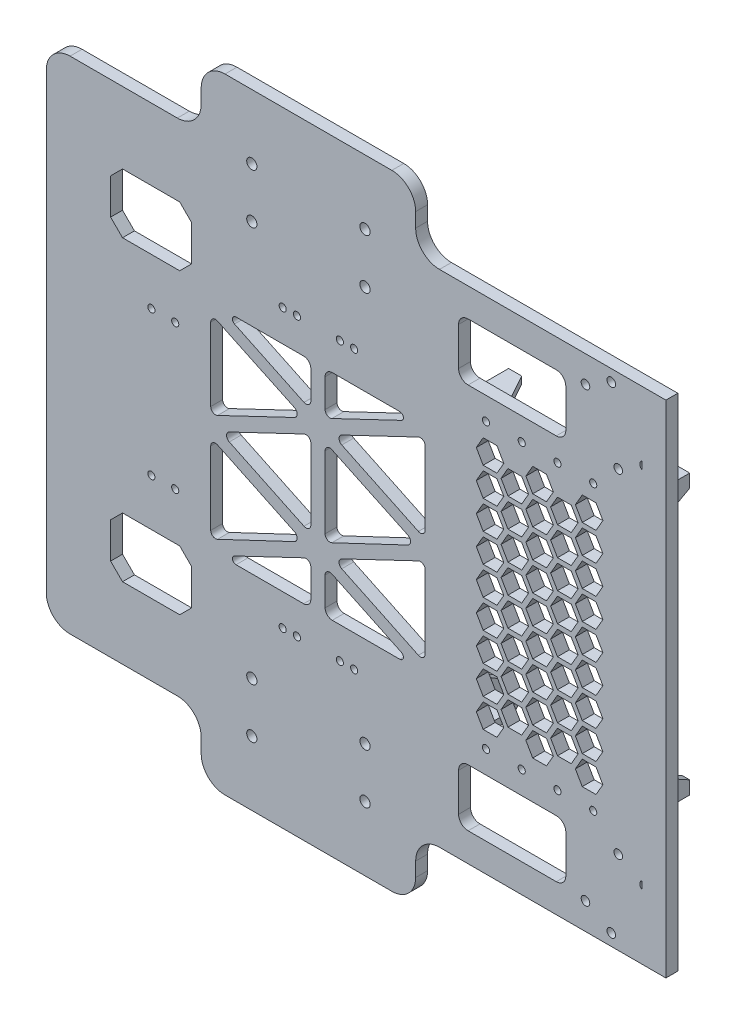
SolidWorks part; units mm, degrees
ref_plane "前视基准面" through (0, 0, 0) normal (0, 0, 1) x (1, 0, 0)
ref_plane "上视基准面" through (0, 0, 0) normal (0, 1, 0) x (1, 0, 0)
ref_plane "右视基准面" through (0, 0, 0) normal (1, 0, 0) x (0, 0, -1)
sketch "草图1" plane through (0, 0, 0) normal (0, 0, 1) x (1, 0, 0)
  line L2 (-130, 95) -> (-130, -95)
  line L3 (-120, -105) -> (-75, -105)
  line L4 (130, 95) -> (130, -95)
  line L5 (126.7518, 102.3765) -> (130, 105) construction
  line L6 (-130, -105) -> (-126.7518, -102.3765) construction
  line L9 (-65, -115) -> (-65, -121)
  line L10 (-55, -131) -> (15, -131)
  line L11 (25, -121) -> (25, -115)
  line L13 (35, -105) -> (120, -105)
  line L14 (126.7518, -102.3765) -> (130, -105) construction
  line L15 (-130, 105) -> (-126.7518, 102.3765) construction
  line L16 (-130, 0) -> (130, 0) construction
  line L17 (35, 105) -> (120, 105)
  line L18 (25, 121) -> (25, 115)
  line L19 (-55, 131) -> (15, 131)
  line L20 (-65, 115) -> (-65, 121)
  line L21 (-120, 105) -> (-75, 105)
  arc A1 (-120, -105) -> (-130, -95) centre (-120, -95) cw
  arc A3 (120, -105) -> (130, -95) centre (120, -95) ccw
  arc A8 (-65, -115) -> (-75, -105) centre (-75, -115) ccw
  arc A9 (25, -115) -> (35, -105) centre (35, -115) cw
  arc A10 (-55, -131) -> (-65, -121) centre (-55, -121) cw
  arc A11 (15, -131) -> (25, -121) centre (15, -121) ccw
  arc A12 (15, 131) -> (25, 121) centre (15, 121) cw
  arc A13 (-55, 131) -> (-65, 121) centre (-55, 121) ccw
  arc A14 (25, 115) -> (35, 105) centre (35, 115) ccw
  arc A15 (-65, 115) -> (-75, 105) centre (-75, 115) cw
  arc A16 (120, 105) -> (130, 95) centre (120, 95) cw
  arc A17 (-120, 105) -> (-130, 95) centre (-120, 95) ccw
  point P0 (0, 0)
  point P40 (25, -105)
  point P45 (25, 105)
  dimension "D2" = 10
  dimension "D3" = 65
  dimension "D4" = 10
  dimension "D5" = 105
  dimension "D7" = 10
  dimension "D8" = 10
  dimension "D10" = 10
  dimension "D12" = 10
  dimension "D13" = 105
  dimension "D18" = 90
  dimension "D19" = 6
extrude "凸台-拉伸1" add sketch "草图1" along normal blind 5
sketch "草图4" plane through (0, 0, 0) normal (0, 0, -1) x (-1, 0, 0)
  line L0 (-39, -47.5) -> (-39, -58.5)
  line L1 (-39, -58.5) -> (-50, -58.5)
  line L2 (-50, -58.5) -> (-50, -55.5)
  line L3 (-50, -55.5) -> (-42, -55.5)
  line L4 (-42, -55.5) -> (-42, -47.5)
  line L5 (-42, -47.5) -> (-39, -47.5)
  line L6 (-130, 0) -> (-25.5592, 0) construction
  line L7 (-130, -95) -> (-130, 95) construction
  line L10 (-130, -95) -> (-130, 95) construction
  dimension "D1" = 11
  dimension "D2" = 11
  dimension "D3" = 3
  dimension "D4" = 3
  dimension "D5" = 80
  dimension "D7" = 55.5
extrude "凸台-拉伸2" add sketch "草图4" along normal blind 20
sketch "草图5" plane through (0, -58.5, 0) normal (0, -1, 0) x (1, 0, 0)
  line L0 (50, -10) -> (44.5, -20)
  line L1 (50, -20) -> (50, 0) construction
  line L2 (50, -20) -> (39, -20) construction
  line L3 (44.5, -20) -> (50, -20)
  line L4 (50, -20) -> (50, -10)
  dimension "D1" = 10
  dimension "D2" = 5.5
extrude "切除-拉伸3" cut sketch "草图5" against normal blind 10
sketch "草图6" plane through (39, 0, 0) normal (-1, 0, 0) x (0, 0, 1)
  line L0 (-20, -53) -> (-10, -47.5)
  line L1 (-20, -58.5) -> (-20, -47.5) construction
  line L2 (-20, -47.5) -> (0, -47.5) construction
  line L3 (-10, -47.5) -> (-20, -47.5)
  line L4 (-20, -47.5) -> (-20, -53)
  dimension "D1" = 10
  dimension "D2" = 5.5
extrude "切除-拉伸4" cut sketch "草图6" against normal blind 10
ref_plane "基准面2" through (77, 0, 0) normal (1, 0, 0) x (0, 0, -1)
mirror "镜向1" about plane through (77, 0, 0) normal (1, 0, 0) of "凸台-拉伸2", "切除-拉伸4", "切除-拉伸3"
mirror "镜向2" about plane through (0, 0, 0) normal (0, 1, 0) of "镜向1"
sketch "草图7" plane through (0, 0, 0) normal (0, 0, -1) x (-1, 0, 0)
  line L4 (-112, -55.5) -> (-104, -55.5) construction
  line L5 (-112, 47.5) -> (-112, 55.5) construction
  line L6 (-112, 55.5) -> (-104, 55.5) construction
  line L7 (-92.013, 36) -> (-94.8997, 41)
  line L8 (-94.8997, 41) -> (-100.6732, 41)
  line L9 (-100.6732, 41) -> (-103.56, 36)
  line L10 (-103.56, 36) -> (-100.6732, 31)
  line L11 (-100.6732, 31) -> (-94.8997, 31)
  line L12 (-94.8997, 31) -> (-92.013, 36)
  line L13 (-77.0019, 36) -> (-97.7865, 36) construction
  line L14 (-74.1151, 31) -> (-71.2284, 36)
  line L15 (-71.2284, 36) -> (-74.1151, 41)
  line L16 (-74.1151, 41) -> (-79.8886, 41)
  line L17 (-79.8886, 41) -> (-82.7754, 36)
  line L18 (-82.7754, 36) -> (-79.8886, 31)
  line L19 (-79.8886, 31) -> (-74.1151, 31)
  line L20 (-92.013, 24) -> (-94.8997, 29)
  line L21 (-93.1677, 30) -> (-90.2809, 25)
  line L22 (-90.2809, 25) -> (-84.5074, 25)
  line L23 (-84.5074, 25) -> (-81.6207, 30)
  line L24 (-81.6207, 30) -> (-84.5074, 35)
  line L25 (-84.5074, 35) -> (-90.2809, 35)
  line L26 (-90.2809, 35) -> (-93.1677, 30)
  line L27 (-84.5074, 37) -> (-81.6207, 42)
  line L28 (-81.6207, 42) -> (-84.5074, 47)
  line L29 (-84.5074, 47) -> (-90.2809, 47)
  line L30 (-90.2809, 47) -> (-93.1677, 42)
  line L31 (-93.1677, 42) -> (-90.2809, 37)
  line L32 (-90.2809, 37) -> (-84.5074, 37)
  line L33 (-79.8886, 43) -> (-74.1151, 43)
  line L34 (-74.1151, 43) -> (-71.2284, 48)
  line L35 (-71.2284, 48) -> (-74.1151, 53)
  line L36 (-74.1151, 53) -> (-79.8886, 53)
  line L37 (-79.8886, 53) -> (-82.7754, 48)
  line L38 (-82.7754, 48) -> (-79.8886, 43)
  line L39 (-94.8997, 43) -> (-92.013, 48)
  line L40 (-92.013, 48) -> (-94.8997, 53)
  line L41 (-94.8997, 53) -> (-100.6732, 53)
  line L42 (-100.6732, 53) -> (-103.56, 48)
  line L43 (-103.56, 48) -> (-100.6732, 43)
  line L44 (-100.6732, 43) -> (-94.8997, 43)
  line L45 (-72.3831, 42) -> (-69.4963, 37)
  line L46 (-69.4963, 37) -> (-63.7228, 37)
  line L47 (-63.7228, 37) -> (-60.8361, 42)
  line L48 (-60.8361, 42) -> (-63.7228, 47)
  line L49 (-63.7228, 47) -> (-69.4963, 47)
  line L50 (-69.4963, 47) -> (-72.3831, 42)
  line L51 (-94.8997, 29) -> (-100.6732, 29)
  line L52 (-100.6732, 29) -> (-103.56, 24)
  line L53 (-103.56, 24) -> (-100.6732, 19)
  line L54 (-100.6732, 19) -> (-94.8997, 19)
  line L55 (-94.8997, 19) -> (-92.013, 24)
  line L56 (-93.1677, 18) -> (-90.2809, 13)
  line L57 (-90.2809, 13) -> (-84.5074, 13)
  line L58 (-84.5074, 13) -> (-81.6207, 18)
  line L59 (-81.6207, 18) -> (-84.5074, 23)
  line L60 (-84.5074, 23) -> (-90.2809, 23)
  line L61 (-90.2809, 23) -> (-93.1677, 18)
  line L62 (-74.1151, 19) -> (-71.2284, 24)
  line L63 (-71.2284, 24) -> (-74.1151, 29)
  line L64 (-74.1151, 29) -> (-79.8886, 29)
  line L65 (-79.8886, 29) -> (-82.7754, 24)
  line L66 (-82.7754, 24) -> (-79.8886, 19)
  line L67 (-79.8886, 19) -> (-74.1151, 19)
  line L68 (-72.3831, 30) -> (-69.4963, 25)
  line L69 (-69.4963, 25) -> (-63.7228, 25)
  line L70 (-63.7228, 25) -> (-60.8361, 30)
  line L71 (-60.8361, 30) -> (-63.7228, 35)
  line L72 (-63.7228, 35) -> (-69.4963, 35)
  line L73 (-69.4963, 35) -> (-72.3831, 30)
  line L74 (-92.013, 12) -> (-94.8997, 17)
  line L75 (-94.8997, 17) -> (-100.6732, 17)
  line L76 (-100.6732, 17) -> (-103.56, 12)
  line L77 (-103.56, 12) -> (-100.6732, 7)
  line L78 (-100.6732, 7) -> (-94.8997, 7)
  line L79 (-94.8997, 7) -> (-92.013, 12)
  line L80 (-93.1677, 6) -> (-90.2809, 1)
  line L81 (-90.2809, 1) -> (-84.5074, 1)
  line L82 (-84.5074, 1) -> (-81.6207, 6)
  line L83 (-81.6207, 6) -> (-84.5074, 11)
  line L84 (-84.5074, 11) -> (-90.2809, 11)
  line L85 (-90.2809, 11) -> (-93.1677, 6)
  line L86 (-74.1151, 7) -> (-71.2284, 12)
  line L87 (-71.2284, 12) -> (-74.1151, 17)
  line L88 (-74.1151, 17) -> (-79.8886, 17)
  line L89 (-79.8886, 17) -> (-82.7754, 12)
  line L90 (-82.7754, 12) -> (-79.8886, 7)
  line L91 (-79.8886, 7) -> (-74.1151, 7)
  line L92 (-72.3831, 18) -> (-69.4963, 13)
  line L93 (-69.4963, 13) -> (-63.7228, 13)
  line L94 (-63.7228, 13) -> (-60.8361, 18)
  line L95 (-60.8361, 18) -> (-63.7228, 23)
  line L96 (-63.7228, 23) -> (-69.4963, 23)
  line L97 (-69.4963, 23) -> (-72.3831, 18)
  line L98 (-92.013, 0) -> (-94.8997, 5)
  line L99 (-94.8997, 5) -> (-100.6732, 5)
  line L100 (-100.6732, 5) -> (-103.56, 0)
  line L101 (-103.56, 0) -> (-100.6732, -5)
  line L102 (-100.6732, -5) -> (-94.8997, -5)
  line L103 (-94.8997, -5) -> (-92.013, 0)
  line L104 (-93.1677, -6) -> (-90.2809, -11)
  line L105 (-90.2809, -11) -> (-84.5074, -11)
  line L106 (-84.5074, -11) -> (-81.6207, -6)
  line L107 (-81.6207, -6) -> (-84.5074, -1)
  line L108 (-84.5074, -1) -> (-90.2809, -1)
  line L109 (-90.2809, -1) -> (-93.1677, -6)
  line L110 (-74.1151, -5) -> (-71.2284, 0)
  line L111 (-71.2284, 0) -> (-74.1151, 5)
  line L112 (-74.1151, 5) -> (-79.8886, 5)
  line L113 (-79.8886, 5) -> (-82.7754, 0)
  line L114 (-82.7754, 0) -> (-79.8886, -5)
  line L115 (-79.8886, -5) -> (-74.1151, -5)
  line L116 (-72.3831, 6) -> (-69.4963, 1)
  line L117 (-69.4963, 1) -> (-63.7228, 1)
  line L118 (-63.7228, 1) -> (-60.8361, 6)
  line L119 (-60.8361, 6) -> (-63.7228, 11)
  line L120 (-63.7228, 11) -> (-69.4963, 11)
  line L121 (-69.4963, 11) -> (-72.3831, 6)
  line L122 (-92.013, -12) -> (-94.8997, -7)
  line L123 (-94.8997, -7) -> (-100.6732, -7)
  line L124 (-100.6732, -7) -> (-103.56, -12)
  line L125 (-103.56, -12) -> (-100.6732, -17)
  line L126 (-100.6732, -17) -> (-94.8997, -17)
  line L127 (-94.8997, -17) -> (-92.013, -12)
  line L128 (-93.1677, -18) -> (-90.2809, -23)
  line L129 (-90.2809, -23) -> (-84.5074, -23)
  line L130 (-84.5074, -23) -> (-81.6207, -18)
  line L131 (-81.6207, -18) -> (-84.5074, -13)
  line L132 (-84.5074, -13) -> (-90.2809, -13)
  line L133 (-90.2809, -13) -> (-93.1677, -18)
  line L134 (-74.1151, -17) -> (-71.2284, -12)
  line L135 (-71.2284, -12) -> (-74.1151, -7)
  line L136 (-74.1151, -7) -> (-79.8886, -7)
  line L137 (-79.8886, -7) -> (-82.7754, -12)
  line L138 (-82.7754, -12) -> (-79.8886, -17)
  line L139 (-79.8886, -17) -> (-74.1151, -17)
  line L140 (-72.3831, -6) -> (-69.4963, -11)
  line L141 (-69.4963, -11) -> (-63.7228, -11)
  line L142 (-63.7228, -11) -> (-60.8361, -6)
  line L143 (-60.8361, -6) -> (-63.7228, -1)
  line L144 (-63.7228, -1) -> (-69.4963, -1)
  line L145 (-69.4963, -1) -> (-72.3831, -6)
  line L146 (-92.013, -24) -> (-94.8997, -19)
  line L147 (-94.8997, -19) -> (-100.6732, -19)
  line L148 (-100.6732, -19) -> (-103.56, -24)
  line L149 (-103.56, -24) -> (-100.6732, -29)
  line L150 (-100.6732, -29) -> (-94.8997, -29)
  line L151 (-94.8997, -29) -> (-92.013, -24)
  line L152 (-93.1677, -30) -> (-90.2809, -35)
  line L153 (-90.2809, -35) -> (-84.5074, -35)
  line L154 (-84.5074, -35) -> (-81.6207, -30)
  line L155 (-81.6207, -30) -> (-84.5074, -25)
  line L156 (-84.5074, -25) -> (-90.2809, -25)
  line L157 (-90.2809, -25) -> (-93.1677, -30)
  line L158 (-74.1151, -29) -> (-71.2284, -24)
  line L159 (-71.2284, -24) -> (-74.1151, -19)
  line L160 (-74.1151, -19) -> (-79.8886, -19)
  line L161 (-79.8886, -19) -> (-82.7754, -24)
  line L162 (-82.7754, -24) -> (-79.8886, -29)
  line L163 (-79.8886, -29) -> (-74.1151, -29)
  line L164 (-72.3831, -18) -> (-69.4963, -23)
  line L165 (-69.4963, -23) -> (-63.7228, -23)
  line L166 (-63.7228, -23) -> (-60.8361, -18)
  line L167 (-60.8361, -18) -> (-63.7228, -13)
  line L168 (-63.7228, -13) -> (-69.4963, -13)
  line L169 (-69.4963, -13) -> (-72.3831, -18)
  line L170 (-92.013, -36) -> (-94.8997, -31)
  line L171 (-94.8997, -31) -> (-100.6732, -31)
  line L172 (-100.6732, -31) -> (-103.56, -36)
  line L173 (-103.56, -36) -> (-100.6732, -41)
  line L174 (-100.6732, -41) -> (-94.8997, -41)
  line L175 (-94.8997, -41) -> (-92.013, -36)
  line L176 (-93.1677, -42) -> (-90.2809, -47)
  line L177 (-90.2809, -47) -> (-84.5074, -47)
  line L178 (-84.5074, -47) -> (-81.6207, -42)
  line L179 (-81.6207, -42) -> (-84.5074, -37)
  line L180 (-84.5074, -37) -> (-90.2809, -37)
  line L181 (-90.2809, -37) -> (-93.1677, -42)
  line L182 (-74.1151, -41) -> (-71.2284, -36)
  line L183 (-71.2284, -36) -> (-74.1151, -31)
  line L184 (-74.1151, -31) -> (-79.8886, -31)
  line L185 (-79.8886, -31) -> (-82.7754, -36)
  line L186 (-82.7754, -36) -> (-79.8886, -41)
  line L187 (-79.8886, -41) -> (-74.1151, -41)
  line L188 (-72.3831, -30) -> (-69.4963, -35)
  line L189 (-69.4963, -35) -> (-63.7228, -35)
  line L190 (-63.7228, -35) -> (-60.8361, -30)
  line L191 (-60.8361, -30) -> (-63.7228, -25)
  line L192 (-63.7228, -25) -> (-69.4963, -25)
  line L193 (-69.4963, -25) -> (-72.3831, -30)
  line L194 (-92.013, -48) -> (-94.8997, -43)
  line L195 (-94.8997, -43) -> (-100.6732, -43)
  line L196 (-100.6732, -43) -> (-103.56, -48)
  line L197 (-103.56, -48) -> (-100.6732, -53)
  line L198 (-100.6732, -53) -> (-94.8997, -53)
  line L199 (-94.8997, -53) -> (-92.013, -48)
  line L206 (-74.1151, -53) -> (-71.2284, -48)
  line L207 (-71.2284, -48) -> (-74.1151, -43)
  line L208 (-74.1151, -43) -> (-79.8886, -43)
  line L209 (-79.8886, -43) -> (-82.7754, -48)
  line L210 (-82.7754, -48) -> (-79.8886, -53)
  line L211 (-79.8886, -53) -> (-74.1151, -53)
  line L212 (-72.3831, -42) -> (-69.4963, -47)
  line L213 (-69.4963, -47) -> (-63.7228, -47)
  line L214 (-63.7228, -47) -> (-60.8361, -42)
  line L215 (-60.8361, -42) -> (-63.7228, -37)
  line L216 (-63.7228, -37) -> (-69.4963, -37)
  line L217 (-69.4963, -37) -> (-72.3831, -42)
  line L218 (-61.9908, 36) -> (-59.104, 31)
  line L219 (-61.9908, 48) -> (-59.104, 43)
  line L220 (-59.104, 43) -> (-53.3305, 43)
  line L221 (-53.3305, 43) -> (-50.4438, 48)
  line L222 (-50.4438, 48) -> (-53.3305, 53)
  line L223 (-53.3305, 53) -> (-59.104, 53)
  line L224 (-59.104, 53) -> (-61.9908, 48)
  line L225 (-59.104, 31) -> (-53.3305, 31)
  line L226 (-53.3305, 31) -> (-50.4438, 36)
  line L227 (-50.4438, 36) -> (-53.3305, 41)
  line L228 (-53.3305, 41) -> (-59.104, 41)
  line L229 (-59.104, 41) -> (-61.9908, 36)
  line L230 (-61.9908, 24) -> (-59.104, 19)
  line L231 (-59.104, 19) -> (-53.3305, 19)
  line L232 (-53.3305, 19) -> (-50.4438, 24)
  line L233 (-50.4438, 24) -> (-53.3305, 29)
  line L234 (-53.3305, 29) -> (-59.104, 29)
  line L235 (-59.104, 29) -> (-61.9908, 24)
  line L236 (-61.9908, 12) -> (-59.104, 7)
  line L237 (-59.104, 7) -> (-53.3305, 7)
  line L238 (-53.3305, 7) -> (-50.4438, 12)
  line L239 (-50.4438, 12) -> (-53.3305, 17)
  line L240 (-53.3305, 17) -> (-59.104, 17)
  line L241 (-59.104, 17) -> (-61.9908, 12)
  line L242 (-61.9908, 0) -> (-59.104, -5)
  line L243 (-59.104, -5) -> (-53.3305, -5)
  line L244 (-53.3305, -5) -> (-50.4438, 0)
  line L245 (-50.4438, 0) -> (-53.3305, 5)
  line L246 (-53.3305, 5) -> (-59.104, 5)
  line L247 (-59.104, 5) -> (-61.9908, 0)
  line L248 (-61.9908, -12) -> (-59.104, -17)
  line L249 (-59.104, -17) -> (-53.3305, -17)
  line L250 (-53.3305, -17) -> (-50.4438, -12)
  line L251 (-50.4438, -12) -> (-53.3305, -7)
  line L252 (-53.3305, -7) -> (-59.104, -7)
  line L253 (-59.104, -7) -> (-61.9908, -12)
  line L254 (-61.9908, -24) -> (-59.104, -29)
  line L255 (-59.104, -29) -> (-53.3305, -29)
  line L256 (-53.3305, -29) -> (-50.4438, -24)
  line L257 (-50.4438, -24) -> (-53.3305, -19)
  line L258 (-53.3305, -19) -> (-59.104, -19)
  line L259 (-59.104, -19) -> (-61.9908, -24)
  line L260 (-61.9908, -36) -> (-59.104, -41)
  line L261 (-59.104, -41) -> (-53.3305, -41)
  line L262 (-53.3305, -41) -> (-50.4438, -36)
  line L263 (-50.4438, -36) -> (-53.3305, -31)
  line L264 (-53.3305, -31) -> (-59.104, -31)
  line L265 (-59.104, -31) -> (-61.9908, -36)
  line L266 (-61.9908, -48) -> (-59.104, -53)
  line L267 (-59.104, -53) -> (-53.3305, -53)
  line L268 (-53.3305, -53) -> (-50.4438, -48)
  line L269 (-50.4438, -48) -> (-53.3305, -43)
  line L270 (-53.3305, -43) -> (-59.104, -43)
  line L271 (-59.104, -43) -> (-61.9908, -48)
  line L272 (-93.1677, -54) -> (-90.2809, -59) [skipped]
  line L273 (-90.2809, -59) -> (-84.5074, -59) [skipped]
  line L274 (-84.5074, -59) -> (-81.6207, -54) [skipped]
  line L275 (-81.6207, -54) -> (-84.5074, -49) [skipped]
  line L276 (-84.5074, -49) -> (-90.2809, -49) [skipped]
  line L277 (-90.2809, -49) -> (-93.1677, -54) [skipped]
  circle A0 centre (-97.7865, 36) radius 5 construction
  circle A1 centre (-77.0019, 36) radius 5 construction
  circle A2 centre (-87.3942, 30) radius 5 construction
  circle A3 centre (-87.3942, 42) radius 5 construction
  circle A4 centre (-77.0019, 48) radius 5 construction
  circle A5 centre (-97.7865, 48) radius 5 construction
  circle A6 centre (-66.6096, 42) radius 5 construction
  circle A7 centre (-56.2173, 48) radius 5 construction
  point P4 (-87.3942, 37)
  dimension "D1" = 2
  dimension "D3" = 10
  dimension "D4" = 10
  dimension "D5" = 2
  dimension "D7" = 10
  dimension "D11" = 10
  dimension "D14" = 10
  dimension "D15" = 10
  dimension "D20" = 10
  dimension "D2" = 2
  dimension "D6" = 2
  dimension "D8" = 2
  dimension "D9" = 2
  dimension "D10" = 2
  dimension "D12" = 2
  dimension "D13" = 2
  dimension "D16" = 2
  dimension "D17" = 2
  dimension "D19" = 2
  dimension "D21" = 9
  dimension "D22" = 2.5
  dimension "D23" = 2.5
  dimension "D24" = 8.44
  dimension "D18" = 8
extrude "切除-拉伸5" cut sketch "草图7" against normal blind 5
sketch "草图8" plane through (0, 0, 0) normal (0, 0, -1) x (-1, 0, 0)
  line L0 (-75.3677, 120) -> (-75.3677, -120)
  line L1 (-100.0285, 77.2863) -> (-100.0285, -77.2863)
  line L2 (-100.0285, 77.2863) -> (-75.3677, 120)
  line L3 (-100.0285, -77.2863) -> (-75.3677, -120)
  line L4 (-37.1297, 0) -> (-146.8562, 0) construction
  dimension "D1" = 30
  dimension "D2" = 30
  dimension "D3" = 120
  dimension "D4" = 120
sketch "草图9" plane through (0, 0, 0) normal (0, 0, -1) x (-1, 0, 0)
  line L0 (148.8518, 0) -> (-37.1297, 0) construction
  line L1 (-29, 41) -> (-29, 4)
  line L2 (-25, -45) -> (13, -45)
  line L3 (61, -41) -> (61, -4)
  line L4 (57, 45) -> (19, 45)
  line L14 (-29, 41) -> (9.8049, 22.5)
  line L15 (57, 0) -> (19, -18.1163)
  line L16 (130, 95) -> (130, -95) construction
  line L17 (63, 93) -> (118, 93)
  line L18 (63, 93) -> (63, 66)
  line L19 (63, 66) -> (118, 66)
  line L20 (118, 93) -> (118, 66)
  line L21 (75, 105) -> (120, 105) construction
  line L22 (63, -66) -> (118, -66)
  line L23 (118, -93) -> (118, -66)
  line L24 (63, -93) -> (118, -93)
  line L25 (63, -93) -> (63, -66)
  line L26 (-120, 105) -> (-35, 105) construction
  line L27 (-43, 93) -> (-88, 93)
  line L28 (-43, 93) -> (-43, 69)
  line L29 (-43, 69) -> (-88, 69)
  line L30 (-88, 93) -> (-88, 69)
  line L31 (-130, -95) -> (-130, 95) construction
  line L32 (-43, -69) -> (-88, -69)
  line L33 (-88, -93) -> (-88, -69)
  line L34 (-43, -93) -> (-88, -93)
  line L35 (-43, -93) -> (-43, -69)
  line L36 (-25, 45) -> (13, 26.8837)
  line L37 (-25, -45) -> (13, -26.8837)
  line L38 (61, 41) -> (22.0746, 22.5575)
  line L39 (-25.5359, 0) -> (13, -18.258)
  line L40 (57, 45) -> (19, 26.8837)
  line L41 (57, -45) -> (19, -26.8837)
  line L42 (16, 61.4977) -> (16, -60.5731) construction
  line L43 (13, 45) -> (13, 26.8837)
  line L44 (19, 45) -> (19, 26.8837)
  line L45 (13, 18.258) -> (13, -18.258)
  line L46 (9.8049, 22.5) -> (-29, 4)
  line L47 (19, 18.1163) -> (57, 0)
  line L48 (22.0746, 22.5575) -> (61, 4)
  line L49 (13, 18.258) -> (-25.5359, 0)
  line L50 (19, 18.1163) -> (19, -18.1163)
  line L51 (22.0746, -22.5575) -> (61, -41)
  line L52 (9.8049, -22.5) -> (-29, -41)
  line L53 (9.8049, -22.5) -> (-29, -4)
  line L54 (22.0746, -22.5575) -> (61, -4)
  line L55 (13, -26.8837) -> (13, -45)
  line L56 (19, -26.8837) -> (19, -45)
  line L57 (13, 45) -> (-25, 45)
  line L58 (-29, -4) -> (-29, -41)
  line L59 (19, -45) -> (57, -45)
  line L60 (61, 4) -> (61, 41)
  line L61 (-44, 41) -> (-44, -37.8122) construction
  dimension "D1" = 45
  dimension "D2" = 45
  dimension "D3" = 15
  dimension "D4" = 90
  dimension "D5" = 1
  dimension "D7" = 12
  dimension "D8" = 12
  dimension "D9" = 27
  dimension "D10" = 55
  dimension "D11" = 12
  dimension "D12" = 45
  dimension "D13" = 42
  dimension "D14" = 24
  dimension "D21" = 4
  dimension "D22" = 4
  dimension "D23" = 4
  dimension "D24" = 4
  dimension "D26" = 4
  dimension "D27" = 3
  dimension "D28" = 45
extrude "切除-拉伸6" cut sketch "草图9" against normal blind 5 contours L27 L30 L29 L28 | L34 L35 L32 L33 | L4 L44 L40 | L48 L60 L38 | L47 L50 L15 | L54 L51 L3 | L56 L59 L41 | L55 L37 L2 | L53 L58 L52 | L45 L49 L39 | L46 L14 L1 | L43 L57 L36 | L57 L36 L43 region at (16.065, 22.5, 0) region at (-0.3333, -38.9612, 0) region at (-48.0249, -22.5192, 0) region at (-31.6667, 38.9612, 0) region at (-31.6667, 0, 0) region at (65.5, 81, 0) region at (65.5, -81, 0) region at (-0.3333, 38.9612, 0) region at (-48.0249, 22.5192, 0) region at (-0.1547, 0, 0) region at (-31.6667, -38.9612, 0) region at (16.065, -22.5, 0)
fillet "圆角1" radius 4 8 edges at (43, -93, 2.5) (88, -69, 2.5) (43, -69, 2.5) (88, -93, 2.5) (88, 69, 2.5) (43, 69, 2.5) (43, 93, 2.5) (88, 93, 2.5)
fillet "圆角2" radius 1.5 4 edges at (25, -45, 2.5) (-57, -45, 2.5) (25, 45, 2.5) (-57, 45, 2.5)
fillet "圆角3" radius 2 22 edges at (29, -4, 2.5) (29, 4, 2.5) (-13, -18.258, 2.5) (-61, -41, 2.5) (-61, 4, 2.5) (-13, -26.8837, 2.5) (-13, 18.258, 2.5) (-61, -4, 2.5) (-22.0746, -22.5575, 2.5) (25.5359, 0, 2.5) (-22.0746, 22.5575, 2.5) (-61, 41, 2.5) (-19, 26.8837, 2.5) (-19, -26.8837, 2.5) (-19, -18.1163, 2.5) (29, -41, 2.5) (29, 41, 2.5) (-57, 0, 2.5) (-9.8049, -22.5, 2.5) (-13, 26.8837, 2.5) (-9.8049, 22.5, 2.5) (-19, 18.1163, 2.5)
fillet "圆角4" radius 3 4 edges at (-13, -45, 2.5) (-13, 45, 2.5) (-19, -45, 2.5) (-19, 45, 2.5)
sketch "草图10" plane through (0, 0, 0) normal (0, 0, -1) x (-1, 0, 0)
  line L0 (-37.1297, 0) -> (-146.8562, 0) construction
  line L1 (-37.1297, 0) -> (-146.8562, 0) construction
  circle A0 centre (-120.8289, 76.259) radius 1.8 construction
  circle A1 centre (-110.0035, 70.009) radius 1.8 construction
  circle A2 centre (-107.0789, 100.0747) radius 1.8 construction
  circle A3 centre (-96.2535, 93.8247) radius 1.8 construction
  circle A4 centre (-3.75, 104) radius 2.15 construction
  circle A5 centre (-3.75, 104) radius 2.15
  circle A6 centre (-3.75, -104) radius 2.15
  circle A15 centre (-120.8289, 76.259) radius 1.8
  circle A16 centre (-110.0035, 70.009) radius 1.8
  circle A17 centre (-107.0789, 100.0747) radius 1.8
  circle A18 centre (-96.2535, 93.8247) radius 1.8
  circle A41 centre (-96.2535, -93.8247) radius 1.8
  circle A42 centre (-107.0789, -100.0747) radius 1.8
  circle A43 centre (-110.0035, -70.009) radius 1.8
  circle A44 centre (-120.8289, -76.259) radius 1.8
  circle A45 centre (-99.5, 59.5) radius 1.5 construction
  circle A46 centre (-84.5, 59.5) radius 1.5 construction
  circle A47 centre (-69.5, 59.5) radius 1.5 construction
  circle A48 centre (-54.5, 59.5) radius 1.5 construction
  circle A49 centre (0.8061, 58.25) radius 1.5 construction
  circle A50 centre (6.8061, 58.25) radius 1.5 construction
  circle A51 centre (24.8061, 58.25) radius 1.5 construction
  circle A52 centre (30.8061, 58.25) radius 1.5 construction
  circle A53 centre (-99.5, 59.5) radius 1.5
  circle A54 centre (-84.5, 59.5) radius 1.5
  circle A55 centre (-69.5, 59.5) radius 1.5
  circle A56 centre (-54.5, 59.5) radius 1.5
  circle A57 centre (0.8061, 58.25) radius 1.5
  circle A58 centre (6.8061, 58.25) radius 1.5
  circle A59 centre (24.8061, 58.25) radius 1.5
  circle A60 centre (30.8061, 58.25) radius 1.5
  circle A61 centre (30.8061, -58.25) radius 1.5
  circle A62 centre (24.8061, -58.25) radius 1.5
  circle A63 centre (6.8061, -58.25) radius 1.5
  circle A64 centre (0.8061, -58.25) radius 1.5
  circle A65 centre (-54.5, -59.5) radius 1.5
  circle A66 centre (-69.5, -59.5) radius 1.5
  circle A67 centre (-84.5, -59.5) radius 1.5
  circle A68 centre (-99.5, -59.5) radius 1.5
  circle A89 centre (75.897, 30.3) radius 1.5 construction
  circle A90 centre (85.897, 30.3) radius 1.5 construction
  circle A91 centre (75.897, 30.3) radius 1.5
  circle A92 centre (85.897, 30.3) radius 1.5
  circle A93 centre (85.897, -30.3) radius 1.5
  circle A94 centre (75.897, -30.3) radius 1.5
  circle A95 centre (43.75, 83) radius 2.15 construction
  circle A96 centre (43.75, 104) radius 2.15 construction
  circle A97 centre (-3.75, 83) radius 2.15 construction
  circle A99 centre (43.75, 83) radius 2.15
  circle A100 centre (43.75, 104) radius 2.15
  circle A101 centre (-3.75, 83) radius 2.15
  circle A104 centre (-3.75, -83) radius 2.15
  circle A105 centre (43.75, -104) radius 2.15
  circle A106 centre (43.75, -83) radius 2.15
extrude "切除-拉伸7" cut sketch "草图10" against normal through all
sketch "草图11" plane through (0, 0, 0) normal (0, 0, -1) x (-1, 0, 0)
  line L0 (130, 95) -> (130, -95) construction
  line L1 (74, -75) -> (98, -75)
  line L2 (69, -70) -> (69, -55)
  line L3 (74, -50) -> (98, -50)
  line L4 (103, -70) -> (103, -55)
  line L5 (130, 0) -> (108.529, 0) construction
  line L10 (69, -70) -> (74, -75)
  line L11 (69, -55) -> (74, -50)
  line L12 (98, -50) -> (103, -55)
  line L13 (98, -75) -> (103, -70)
  line L14 (98, 75) -> (103, 70)
  line L15 (98, 50) -> (103, 55)
  line L16 (69, 55) -> (74, 50)
  line L17 (69, 70) -> (74, 75)
  line L18 (103, 70) -> (103, 55)
  line L19 (74, 50) -> (98, 50)
  line L20 (69, 70) -> (69, 55)
  line L21 (74, 75) -> (98, 75)
  point P0 (69, -75)
  point P1 (103, -50)
  point P2 (69, -50)
  point P3 (103, -75)
  point P8 (103, 75)
  point P9 (69, 50)
  point P10 (103, 50)
  point P11 (69, 75)
  dimension "D1" = 34
  dimension "D2" = 25
  dimension "D3" = 27
  dimension "D4" = 50
extrude "切除-拉伸8" cut sketch "草图11" against normal through all
sketch "草图12" plane through (0, 0, 0) normal (0, 0, -1) x (-1, 0, 0)
  line L1 (-120, 105) -> (-130, 105)
  line L2 (-120, 105) -> (-120, -105)
  line L3 (-120, -105) -> (-130, -105)
  line L4 (-130, 105) -> (-130, -105)
extrude "凸台-拉伸3" add sketch "草图12" against normal up to surface (5 mm away) up to face at (-86, -62.5, 5)
equation "\"45、\"=43.7672"
